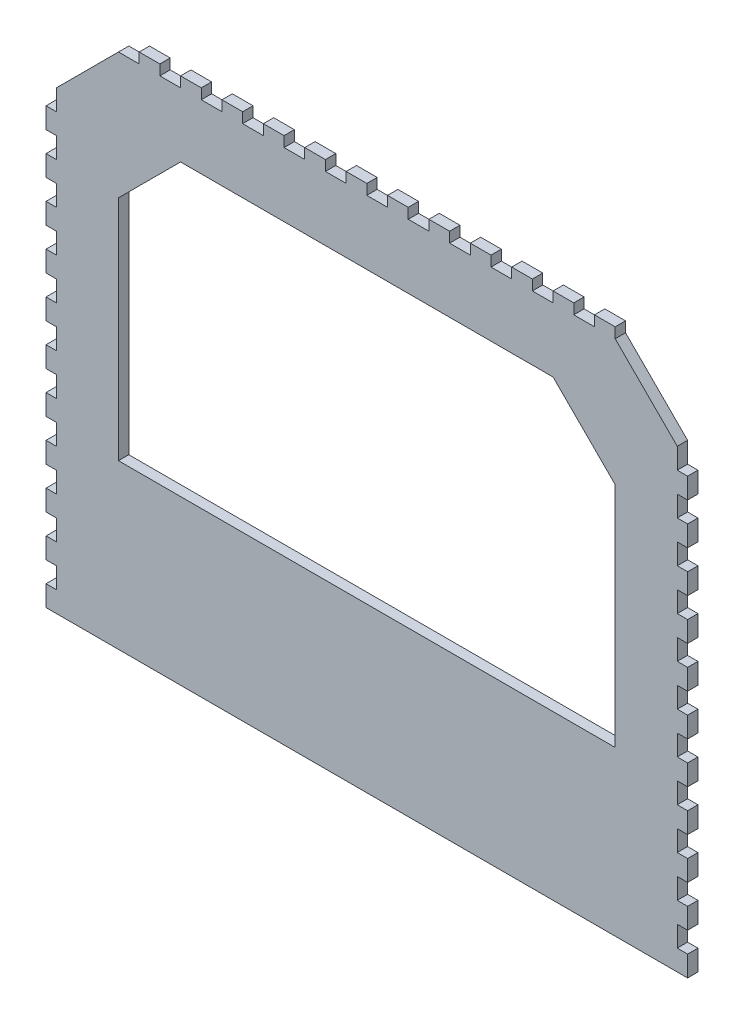
SolidWorks part; units mm, degrees
material "Buche"
ref_plane "Ebene vorne" through (0, 0, 0) normal (0, 0, 1) x (1, 0, 0)
ref_plane "Ebene oben" through (0, 0, 0) normal (0, 1, 0) x (1, 0, 0)
ref_plane "Ebene rechts" through (0, 0, 0) normal (1, 0, 0) x (0, 0, -1)
sketch "Skizze1" plane through (0, 0, 0) normal (0, 0, 1) x (1, 0, 0)
  line L0 (430.8962, 326.3402) -> (430.8962, 336.3402)
  line L1 (430.8962, 316.3402) -> (730.8962, 316.3402)
  line L2 (730.8962, 326.3402) -> (730.8962, 336.3402)
  line L3 (480.8962, 566.3402) -> (490.8962, 566.3402)
  line L4 (430.8962, 536.3402) -> (460.8962, 566.3402)
  line L5 (730.8962, 536.3402) -> (700.8962, 566.3402)
  line L6 (700.8962, 505.3114) -> (670.8962, 535.3114)
  line L7 (460.8962, 395.3114) -> (700.8962, 395.3114)
  line L8 (460.8962, 395.3114) -> (460.8962, 505.3114)
  line L9 (490.8962, 535.3114) -> (670.8962, 535.3114)
  line L10 (700.8962, 395.3114) -> (700.8962, 505.3114)
  line L11 (460.8962, 505.3114) -> (490.8962, 535.3114)
  line L12 (460.8962, 566.3402) -> (470.8962, 566.3402)
  line L13 (730.8962, 316.3402) -> (735.8962, 316.3402)
  line L14 (735.8962, 316.3402) -> (735.8962, 326.3402)
  line L15 (735.8962, 326.3402) -> (730.8962, 326.3402)
  line L16 (730.8962, 346.3402) -> (730.8962, 356.3402)
  line L17 (730.8962, 336.3402) -> (735.8962, 336.3402)
  line L18 (735.8962, 336.3402) -> (735.8962, 346.3402)
  line L19 (735.8962, 346.3402) -> (730.8962, 346.3402)
  line L20 (730.8962, 366.3402) -> (730.8962, 376.3402)
  line L21 (730.8962, 356.3402) -> (735.8962, 356.3402)
  line L22 (735.8962, 356.3402) -> (735.8962, 366.3402)
  line L23 (735.8962, 366.3402) -> (730.8962, 366.3402)
  line L24 (730.8962, 386.3402) -> (730.8962, 396.3402)
  line L25 (730.8962, 376.3402) -> (735.8962, 376.3402)
  line L26 (735.8962, 376.3402) -> (735.8962, 386.3402)
  line L27 (735.8962, 386.3402) -> (730.8962, 386.3402)
  line L28 (730.8962, 406.3402) -> (730.8962, 416.3402)
  line L29 (730.8962, 396.3402) -> (735.8962, 396.3402)
  line L30 (735.8962, 396.3402) -> (735.8962, 406.3402)
  line L31 (735.8962, 406.3402) -> (730.8962, 406.3402)
  line L32 (730.8962, 426.3402) -> (730.8962, 436.3402)
  line L33 (730.8962, 416.3402) -> (735.8962, 416.3402)
  line L34 (735.8962, 416.3402) -> (735.8962, 426.3402)
  line L35 (735.8962, 426.3402) -> (730.8962, 426.3402)
  line L36 (730.8962, 446.3402) -> (730.8962, 456.3402)
  line L37 (730.8962, 436.3402) -> (735.8962, 436.3402)
  line L38 (735.8962, 436.3402) -> (735.8962, 446.3402)
  line L39 (735.8962, 446.3402) -> (730.8962, 446.3402)
  line L40 (730.8962, 466.3402) -> (730.8962, 476.3402)
  line L41 (730.8962, 456.3402) -> (735.8962, 456.3402)
  line L42 (735.8962, 456.3402) -> (735.8962, 466.3402)
  line L43 (735.8962, 466.3402) -> (730.8962, 466.3402)
  line L44 (730.8962, 486.3402) -> (730.8962, 496.3402)
  line L45 (730.8962, 476.3402) -> (735.8962, 476.3402)
  line L46 (735.8962, 476.3402) -> (735.8962, 486.3402)
  line L47 (735.8962, 486.3402) -> (730.8962, 486.3402)
  line L48 (730.8962, 506.3402) -> (730.8962, 516.3402)
  line L49 (730.8962, 496.3402) -> (735.8962, 496.3402)
  line L50 (735.8962, 496.3402) -> (735.8962, 506.3402)
  line L51 (735.8962, 506.3402) -> (730.8962, 506.3402)
  line L52 (730.8962, 526.3402) -> (730.8962, 536.3402)
  line L53 (730.8962, 516.3402) -> (735.8962, 516.3402)
  line L54 (735.8962, 516.3402) -> (735.8962, 526.3402)
  line L55 (735.8962, 526.3402) -> (730.8962, 526.3402)
  line L56 (430.8962, 316.3402) -> (425.8962, 316.3402)
  line L57 (425.8962, 316.3402) -> (425.8962, 326.3402)
  line L58 (425.8962, 326.3402) -> (430.8962, 326.3402)
  line L59 (430.8962, 346.3402) -> (430.8962, 356.3402)
  line L60 (425.8962, 336.3402) -> (425.8962, 346.3402)
  line L61 (425.8962, 346.3402) -> (430.8962, 346.3402)
  line L62 (430.8962, 366.3402) -> (430.8962, 376.3402)
  line L63 (425.8962, 356.3402) -> (425.8962, 366.3402)
  line L64 (425.8962, 366.3402) -> (430.8962, 366.3402)
  line L65 (430.8962, 386.3402) -> (430.8962, 396.3402)
  line L66 (425.8962, 376.3402) -> (425.8962, 386.3402)
  line L67 (425.8962, 386.3402) -> (430.8962, 386.3402)
  line L68 (430.8962, 406.3402) -> (430.8962, 416.3402)
  line L69 (425.8962, 396.3402) -> (425.8962, 406.3402)
  line L70 (425.8962, 406.3402) -> (430.8962, 406.3402)
  line L71 (430.8962, 426.3402) -> (430.8962, 436.3402)
  line L72 (425.8962, 416.3402) -> (425.8962, 426.3402)
  line L73 (425.8962, 426.3402) -> (430.8962, 426.3402)
  line L74 (430.8962, 446.3402) -> (430.8962, 456.3402)
  line L75 (425.8962, 436.3402) -> (425.8962, 446.3402)
  line L76 (425.8962, 446.3402) -> (430.8962, 446.3402)
  line L77 (430.8962, 466.3402) -> (430.8962, 476.3402)
  line L78 (425.8962, 456.3402) -> (425.8962, 466.3402)
  line L79 (425.8962, 466.3402) -> (430.8962, 466.3402)
  line L80 (430.8962, 486.3402) -> (430.8962, 496.3402)
  line L81 (425.8962, 476.3402) -> (425.8962, 486.3402)
  line L82 (425.8962, 486.3402) -> (430.8962, 486.3402)
  line L83 (430.8962, 506.3402) -> (430.8962, 516.3402)
  line L84 (425.8962, 496.3402) -> (425.8962, 506.3402)
  line L85 (425.8962, 506.3402) -> (430.8962, 506.3402)
  line L86 (430.8962, 526.3402) -> (430.8962, 536.3402)
  line L87 (425.8962, 516.3402) -> (425.8962, 526.3402)
  line L88 (425.8962, 526.3402) -> (430.8962, 526.3402)
  line L89 (425.8962, 336.3402) -> (430.8962, 336.3402)
  line L90 (425.8962, 356.3402) -> (430.8962, 356.3402)
  line L91 (425.8962, 376.3402) -> (430.8962, 376.3402)
  line L92 (425.8962, 396.3402) -> (430.8962, 396.3402)
  line L93 (425.8962, 416.3402) -> (430.8962, 416.3402)
  line L94 (425.8962, 436.3402) -> (430.8962, 436.3402)
  line L95 (425.8962, 456.3402) -> (430.8962, 456.3402)
  line L96 (425.8962, 476.3402) -> (430.8962, 476.3402)
  line L97 (425.8962, 496.3402) -> (430.8962, 496.3402)
  line L98 (425.8962, 516.3402) -> (430.8962, 516.3402)
  line L99 (470.8962, 566.3402) -> (470.8962, 571.3402)
  line L100 (470.8962, 571.3402) -> (480.8962, 571.3402)
  line L101 (480.8962, 571.3402) -> (480.8962, 566.3402)
  line L102 (490.8962, 566.3402) -> (490.8962, 571.3402)
  line L103 (490.8962, 571.3402) -> (500.8962, 571.3402)
  line L104 (500.8962, 571.3402) -> (500.8962, 566.3402)
  line L105 (500.8962, 566.3402) -> (510.8962, 566.3402)
  line L106 (510.8962, 566.3402) -> (510.8962, 571.3402)
  line L107 (510.8962, 571.3402) -> (520.8962, 571.3402)
  line L108 (520.8962, 571.3402) -> (520.8962, 566.3402)
  line L109 (520.8962, 566.3402) -> (530.8962, 566.3402)
  line L110 (530.8962, 566.3402) -> (530.8962, 571.3402)
  line L111 (530.8962, 571.3402) -> (540.8962, 571.3402)
  line L112 (540.8962, 571.3402) -> (540.8962, 566.3402)
  line L113 (540.8962, 566.3402) -> (550.8962, 566.3402)
  line L114 (550.8962, 566.3402) -> (550.8962, 571.3402)
  line L115 (550.8962, 571.3402) -> (560.8962, 571.3402)
  line L116 (560.8962, 571.3402) -> (560.8962, 566.3402)
  line L117 (560.8962, 566.3402) -> (570.8962, 566.3402)
  line L118 (570.8962, 566.3402) -> (570.8962, 571.3402)
  line L119 (570.8962, 571.3402) -> (580.8962, 571.3402)
  line L120 (580.8962, 571.3402) -> (580.8962, 566.3402)
  line L121 (580.8962, 566.3402) -> (590.8962, 566.3402)
  line L122 (590.8962, 566.3402) -> (590.8962, 571.3402)
  line L123 (590.8962, 571.3402) -> (600.8962, 571.3402)
  line L124 (600.8962, 571.3402) -> (600.8962, 566.3402)
  line L125 (600.8962, 566.3402) -> (610.8962, 566.3402)
  line L126 (610.8962, 566.3402) -> (610.8962, 571.3402)
  line L127 (610.8962, 571.3402) -> (620.8962, 571.3402)
  line L128 (620.8962, 571.3402) -> (620.8962, 566.3402)
  line L129 (620.8962, 566.3402) -> (630.8962, 566.3402)
  line L130 (630.8962, 566.3402) -> (630.8962, 571.3402)
  line L131 (630.8962, 571.3402) -> (640.8962, 571.3402)
  line L132 (640.8962, 571.3402) -> (640.8962, 566.3402)
  line L133 (640.8962, 566.3402) -> (650.8962, 566.3402)
  line L134 (650.8962, 566.3402) -> (650.8962, 571.3402)
  line L135 (650.8962, 571.3402) -> (660.8962, 571.3402)
  line L136 (660.8962, 571.3402) -> (660.8962, 566.3402)
  line L137 (660.8962, 566.3402) -> (670.8962, 566.3402)
  line L138 (670.8962, 566.3402) -> (670.8962, 571.3402)
  line L139 (670.8962, 571.3402) -> (680.8962, 571.3402)
  line L140 (680.8962, 571.3402) -> (680.8962, 566.3402)
  line L141 (680.8962, 566.3402) -> (690.8962, 566.3402)
  line L142 (690.8962, 566.3402) -> (690.8962, 571.3402)
  line L143 (690.8962, 571.3402) -> (700.8962, 571.3402)
  line L144 (700.8962, 571.3402) -> (700.8962, 566.3402)
  dimension "D1" = 12
extrude "Aufsatz-Linear austragen1" add sketch "Skizze1" along normal blind 5
